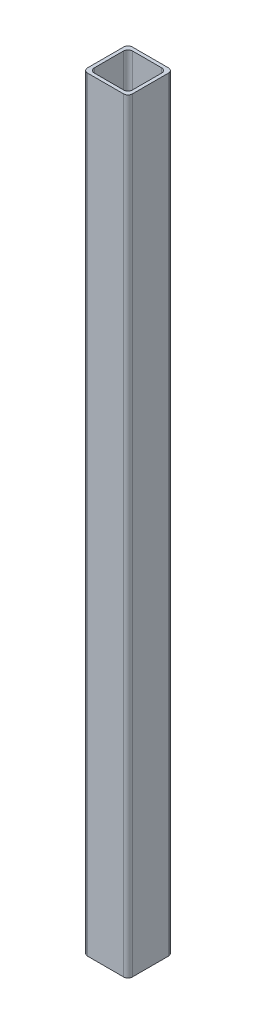
SolidWorks part; units mm, degrees
material "Hexcel AS4C (3000 Filaments)"
ref_plane "Front Plane" through (0, 0, 0) normal (0, 0, 1) x (1, 0, 0)
ref_plane "Top Plane" through (0, 0, 0) normal (0, 1, 0) x (1, 0, 0)
ref_plane "Right Plane" through (0, 0, 0) normal (1, 0, 0) x (0, 0, -1)
sketch "Sketch1" plane through (0, 0, 0) normal (0, 1, 0) x (1, 0, 0)
  line L1 (-4, -5) -> (4, -5)
  line L2 (-5, -4) -> (-5, 4)
  line L3 (-4, 5) -> (4, 5)
  line L4 (5, -4) -> (5, 4)
  line L5 (-5, -5) -> (5, 5) construction
  line L6 (-5, 5) -> (5, -5) construction
  line L7 (-3.25, -4.25) -> (3.25, -4.25)
  line L8 (-4.25, -3.25) -> (-4.25, 3.25)
  line L9 (-3.25, 4.25) -> (3.25, 4.25)
  line L10 (4.25, -3.25) -> (4.25, 3.25)
  line L11 (-4.25, -4.25) -> (4.25, 4.25) construction
  line L12 (-4.25, 4.25) -> (4.25, -4.25) construction
  arc A0 (-4, -5) -> (-5, -4) centre (-4, -4) cw
  arc A1 (4, 5) -> (5, 4) centre (4, 4) cw
  arc A2 (4, -5) -> (5, -4) centre (4, -4) ccw
  arc A3 (-5, 4) -> (-4, 5) centre (-4, 4) cw
  arc A4 (-3.25, -4.25) -> (-4.25, -3.25) centre (-3.25, -3.25) cw
  arc A5 (3.25, -4.25) -> (4.25, -3.25) centre (3.25, -3.25) ccw
  arc A6 (3.25, 4.25) -> (4.25, 3.25) centre (3.25, 3.25) cw
  arc A7 (-4.25, 3.25) -> (-3.25, 4.25) centre (-3.25, 3.25) cw
  point P0 (0, 0)
  point P18 (0, 0)
  dimension "D3" = 1
  dimension "D6" = 1
  dimension "D7" = 1
  dimension "D8" = 1
  dimension "D9" = 1
  dimension "D1" = 10
  dimension "D2" = 10
  dimension "D4" = 8.5
  dimension "D5" = 8.5
extrude "Boss-Extrude1" add sketch "Sketch1" along normal blind 170
